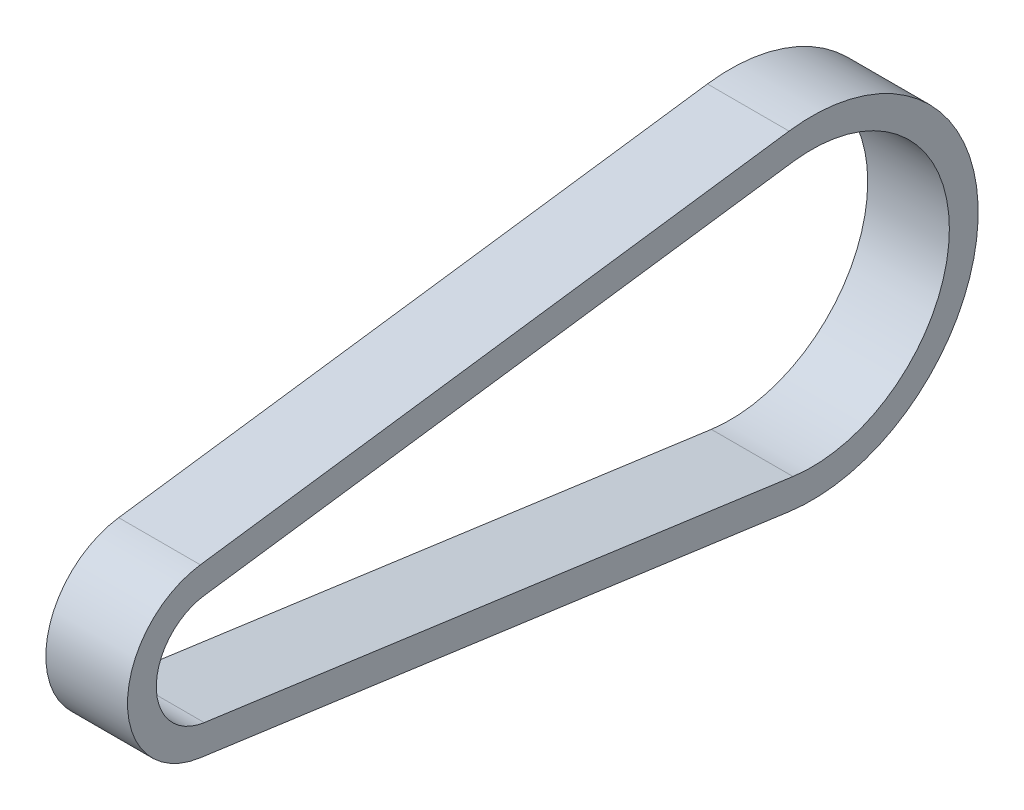
SolidWorks part; units mm, degrees
ref_plane "Front Plane" through (0, 0, 0) normal (0, 0, 1) x (1, 0, 0)
ref_plane "Top Plane" through (0, 0, 0) normal (0, 1, 0) x (1, 0, 0)
ref_plane "Right Plane" through (0, 0, 0) normal (1, 0, 0) x (0, 0, -1)
other "Bounding Box"
ref_plane "Default Plane" through (-8.9266, -12.7485, 0) normal (-0.1736, 0.9848, 0) x (0.9848, 0.1736, 0)
sketch "Sketch1" plane through (0, 0, 0) normal (1, 0, 0) x (0, 0, -1)
  line L0 (0, 0) -> (66.1264, 0) construction
  line L1 (-0.8372, 6.0664) -> (64.0534, 15.0214)
  line L2 (-0.8372, -6.0664) -> (64.0534, -15.0214)
  line L3 (-1.2712, 9.2116) -> (63.6193, 18.1666)
  line L4 (-1.2712, -9.2116) -> (63.6193, -18.1666)
  line L5 (-6.1239, 0) -> (-9.2989, 0) construction
  line L6 (81.2902, 0) -> (84.4652, 0) construction
  arc A0 (-0.8372, 6.0664) -> (-0.8372, -6.0664) centre (0, 0) ccw
  arc A1 (64.0534, -15.0214) -> (64.0534, 15.0214) centre (66.1264, 0) ccw
  arc A2 (-1.2712, 9.2116) -> (-1.2712, -9.2116) centre (0, 0) ccw
  arc A3 (63.6193, -18.1666) -> (63.6193, 18.1666) centre (66.1264, 0) ccw
  dimension "D2" = 3.175
  dimension "D3" = 15.1638
  dimension "D4" = 12.2479
  dimension "D1" = 66.1264
extrude "Boss-Extrude1" add sketch "Sketch1" along normal mid plane 9
